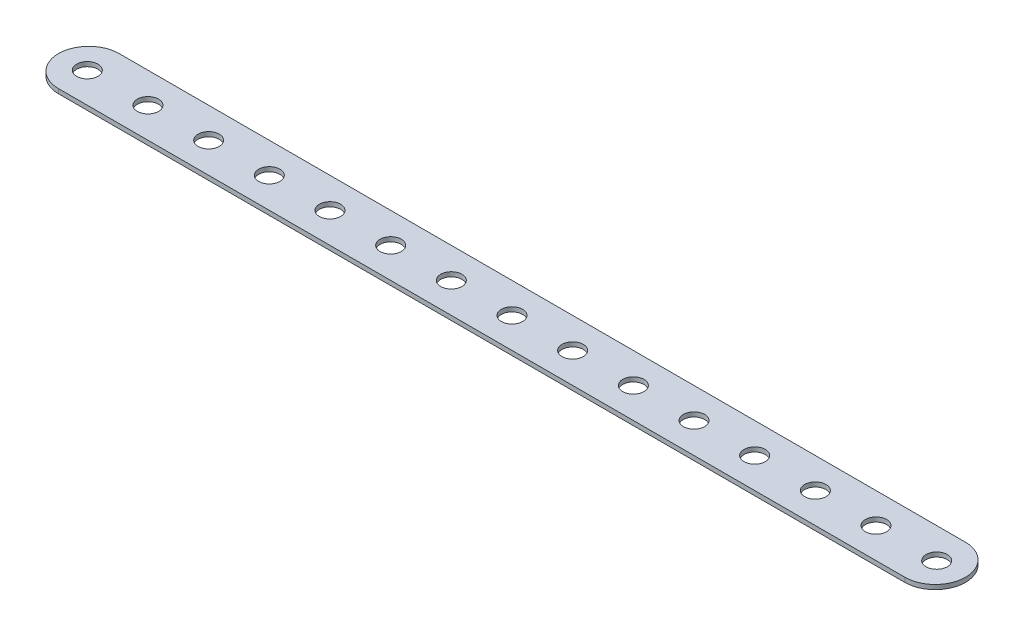
SolidWorks part; units mm, degrees
note: '?' marks a value the reader was unsure of.
ref_plane "Front Plane" through (0, 0, 0) normal (0, 0, 1) x (1, 0, 0)
ref_plane "Top Plane" through (0, 0, 0) normal (0, 1, 0) x (1, 0, 0)
ref_plane "Right Plane" through (0, 0, 0) normal (1, 0, 0) x (0, 0, -1)
ref_plane "Plane1"
sketch "Sketch1" plane through (0, 0, 0) normal (0, 1, 0) x (-1, 0, 0)
  line L0 (177.165, 6.35) -> (0, 6.35)
  line L1 (0, -6.35) -> (177.165, -6.35)
  arc A0 (177.165, -6.35) -> (177.165, 6.35) centre (177.165, 0) ccw
  arc A1 (0, 6.35) -> (0, -6.35) centre (0, 0) ccw
  circle A2 centre (-0.3175, 0) radius 2.2225
  circle A3 centre (177.4825, 0) radius 2.2225
  dimension "D1" = 12.7
  dimension "D3" = 4.445
  dimension "D2" = 177.165
  dimension "D4" = 177.8
extrude "Bar" add sketch "Sketch1" along normal blind 0.9398 contours L0 A1 L1 A0 A3 A2
ref_plane "Plane2" through (0, 0.9398, 0) normal (0, 1, 0) x (1, 0, 0)
sketch "Sketch2" plane through (0, 0.9398, 0) normal (0, 1, 0) x (1, 0, 0)
  circle A0 centre (-164.7825, 0) radius 2.2225
  dimension "D1" = 12.3825
extrude "Center Hole" cut sketch "Sketch2" against normal through all
ref_plane "Plane3" through (0, 0, 0) normal (0, -1, 0) x (-1, 0, 0)
ref_plane "Plane4" through (0, 0, 0) normal (0, 0, 1) x (1, 0, 0)
ref_axis "Axis1" through (-80.9, 0, 0) along (1, 0, 0)?
pattern_linear "Other Center Holes" count 13 spacing 12.7 along (1, 0, 0) of "Center Hole"
